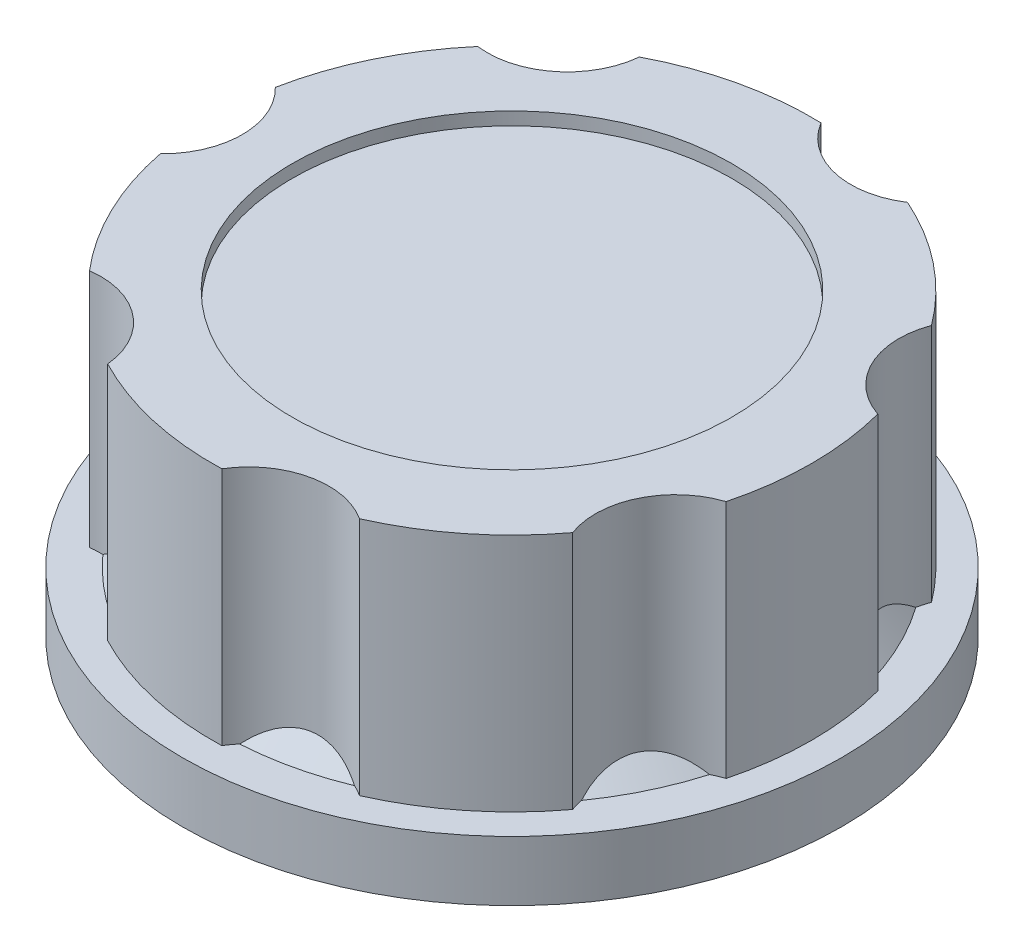
SolidWorks part; units mm, degrees
ref_plane "Front Plane" through (0, 0, 0) normal (0, 0, 1) x (1, 0, 0)
ref_plane "Top Plane" through (0, 0, 0) normal (0, 1, 0) x (1, 0, 0)
ref_plane "Right Plane" through (0, 0, 0) normal (1, 0, 0) x (0, 0, -1)
sketch "Sketch1" plane through (0, 0, 0) normal (1, 0, 0) x (0, 0, -1)
  line L0 (0, 0) -> (-16.5, 0)
  line L1 (-16.5, 0) -> (-16.5, 3)
  line L2 (-16.5, 3) -> (-15, 3)
  line L3 (-15, 3) -> (-15, 15)
  line L4 (-15, 15) -> (-11, 15)
  line L5 (0, 0) -> (0, 15) construction
  line L6 (-11, 15) -> (-11, 14.3557)
  line L7 (-11, 14.3557) -> (0, 14.3557)
  line L8 (0, 0) -> (0, 14.3557)
  dimension "D1" = 33
  dimension "D2" = 30
  dimension "D3" = 3
  dimension "D4" = 12
  dimension "D5" = 0.6443
  dimension "D6" = 4
revolve "Revolve1" add sketch "Sketch1" angle 360 about L8
sketch "Sketch2" plane through (0, 0, 0) normal (0, -1, 0) x (1, 0, 0)
  circle A0 centre (0, 0) radius 3.6
  dimension "D1" = 7.2
extrude "Cut-Extrude1" cut sketch "Sketch2" against normal blind 10
sketch "Sketch3" plane through (0, 15, 0) normal (0, 1, 0) x (1, 0, 0)
  circle A0 centre (-17.5, 0) radius 4
  circle A1 centre (-10.9111, 13.6821) radius 4
  circle A2 centre (3.8941, 17.0612) radius 4
  circle A3 centre (15.767, 7.593) radius 4
  circle A4 centre (15.767, -7.593) radius 4
  circle A5 centre (3.8941, -17.0612) radius 4
  circle A6 centre (-10.9111, -13.6821) radius 4
  dimension "D1" = 8
  dimension "D2" = 17.5
  dimension "D3" = 7
extrude "Cut-Extrude2" cut sketch "Sketch3" against normal blind 11
chamfer "Chamfer1" distance 1.5 angle 45 7 edges at (3.3378, 4, 14.6239) (-9.3523, 4, 11.7275) (-15, 4, 0) (-9.3523, 4, -11.7275) (3.3378, 4, -14.6239) (13.5145, 4, -6.5083) (13.5145, 4, 6.5083)
